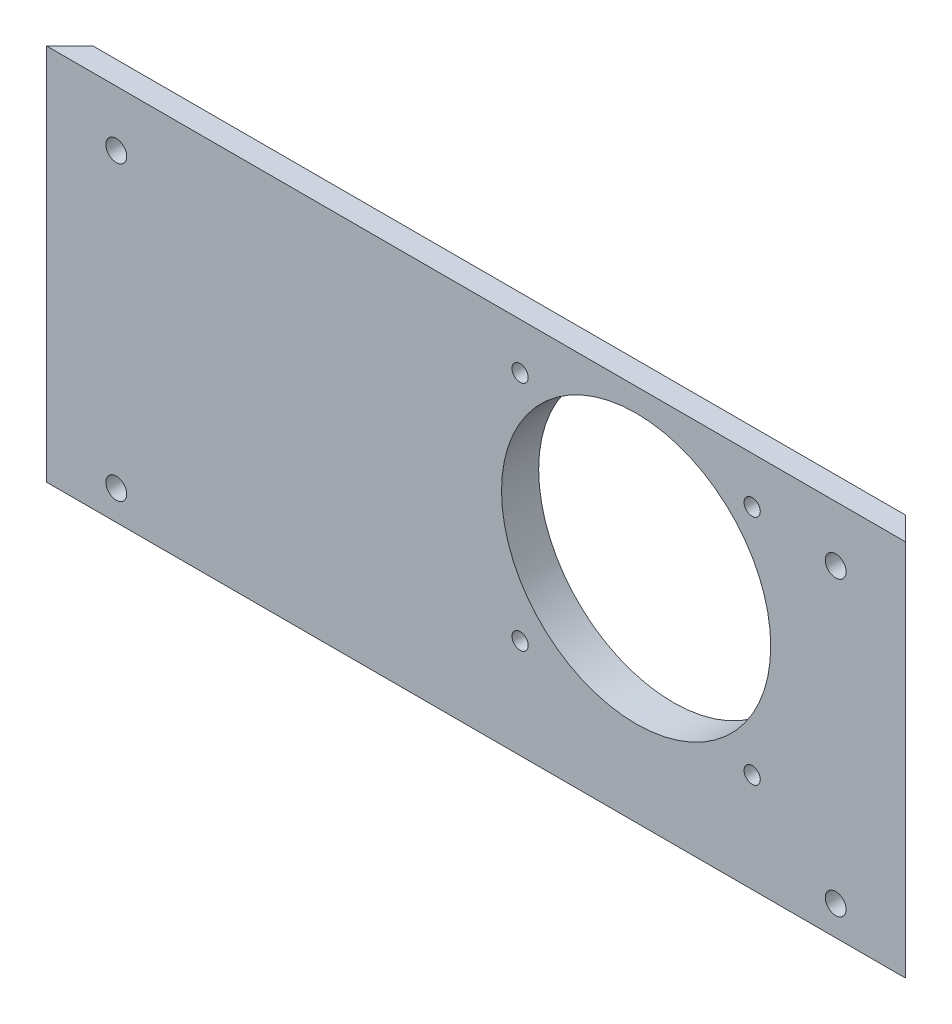
SolidWorks part; units mm, degrees
ref_plane "Front Plane" through (0, 0, 0) normal (0, 0, 1) x (1, 0, 0)
ref_plane "Top Plane" through (0, 0, 0) normal (0, 1, 0) x (1, 0, 0)
ref_plane "Right Plane" through (0, 0, 0) normal (1, 0, 0) x (0, 0, -1)
sketch "Sketch1" plane through (0, 0, 0) normal (0, 0, 1) x (1, 0, 0)
  line L0 (92.5, 84) -> (92.5, -37.3998) construction
  line L1 (0, 0) -> (185, 0)
  line L2 (0, 0) -> (0, 84)
  line L3 (0, 84) -> (185, 84)
  line L4 (185, 0) -> (185, 84)
  line L5 (0, 42) -> (185, 42) construction
  circle A0 centre (15, 9) radius 2.25
  circle A1 centre (170, 9) radius 2.25
  circle A4 centre (15, 72) radius 2.25
  circle A5 centre (170, 72) radius 2.25
  dimension "D3" = 15
  dimension "D5" = 4.5
  dimension "D1" = 84
  dimension "D2" = 185
  dimension "D4" = 9
  dimension "D6" = 2
  dimension "D7" = 12
extrude "Boss-Extrude1" add sketch "Sketch1" against normal blind 5
sketch "Sketch2" plane through (0, 0, -5) normal (0, 0, -1) x (-1, 0, 0)
  line L0 (0, 0) -> (-185, 0) construction
  line L1 (0, 0) -> (-185, 0) construction
  line L2 (0, 5) -> (-185, 5)
  line L3 (-185, 5) -> (-185, 84)
  line L4 (-185, 84) -> (0, 84)
  line L5 (0, 84) -> (0, 5)
  circle A1 centre (-15, 9) radius 2.25 construction
  circle A2 centre (-170, 9) radius 2.25 construction
  circle A5 centre (-15, 9) radius 2.25
  circle A6 centre (-170, 9) radius 2.25
  circle A8 centre (-15, 72) radius 2.25 construction
  circle A9 centre (-170, 72) radius 2.25 construction
  circle A10 centre (-15, 72) radius 2.25
  circle A11 centre (-170, 72) radius 2.25
  dimension "D1" = 5
extrude "Boss-Extrude2" add sketch "Sketch2" along normal blind 3
chamfer "Chamfer1" distance 8 angle 45 3 edges at (185, 44.5, -8) (0, 44.5, -8) (92.5, 84, -8)
chamfer "Chamfer3" distance 3 angle 45 1 edges at (92.5, 84, -8)
sketch "Sketch3" plane through (92.5, 0, -92.5) normal (0.7071, 0, -0.7071) x (-0.7071, 0, -0.7071)
  line L0 (-130.8148, 0) -> (-130.8148, 2.6)
  line L1 (-130.8148, 0) -> (-130.8148, 84) construction
  line L2 (-130.8148, 2.6) -> (-123.7437, 2.6)
  line L4 (-123.7437, 2.6) -> (-123.7437, 0)
  line L5 (-123.7437, 0) -> (-130.8148, 0)
  line L6 (-119.501, 5) -> (-123.7437, 5) construction
  dimension "D1" = 2.4
extrude "Cut-Extrude1" cut sketch "Sketch3" along direction (1, 0, 0) on the side against the normal through all
sketch "Sketch4" plane through (0, 0, 0) normal (0, 0, 1) x (1, 0, 0)
  line L0 (185, 84) -> (0, 84) construction
  line L1 (107, 37) -> (155, 37) construction
  line L2 (107, 37) -> (107, 66) construction
  line L3 (107, 66) -> (155, 66) construction
  line L4 (155, 37) -> (155, 66) construction
  line L5 (185, 2.6) -> (185, 84) construction
  line L6 (131, 71.5) -> (131, 31.5) construction
  line L7 (107, 51.5) -> (155, 51.5) construction
  line L8 (98, 50) -> (97, 50) construction
  line L9 (97, 50) -> (97, 79) construction
  line L10 (97, 79) -> (127, 79) construction
  line L11 (97, 74) -> (102, 74) construction
  line L12 (102, 74) -> (102, 79) construction
  circle A0 centre (127, 50) radius 29
  circle A1 centre (102, 74) radius 1.75
  circle A2 centre (152, 74) radius 1.75
  circle A3 centre (152, 24) radius 1.75
  circle A4 centre (102, 24) radius 1.75
  circle A5 centre (131, 71.5) radius 1.75 construction
  circle A6 centre (131, 31.5) radius 1.75 construction
  point P28 (131, 51.5)
  point P31 (131, 66)
  dimension "D5" = 58
  dimension "D6" = 34
  dimension "D8" = 5
  dimension "D11" = 3.5
  dimension "D16" = 0
  dimension "D1" = 29
  dimension "D2" = 48
  dimension "D3" = 18
  dimension "D4" = 30
  dimension "D7" = 20
  dimension "D9" = 5
  dimension "D10" = 1
  dimension "D14" = 40
  dimension "D15" = 0
  dimension "D12" = 2
  dimension "D13" = 2
extrude "Cut-Extrude2" cut sketch "Sketch4" against normal through all
